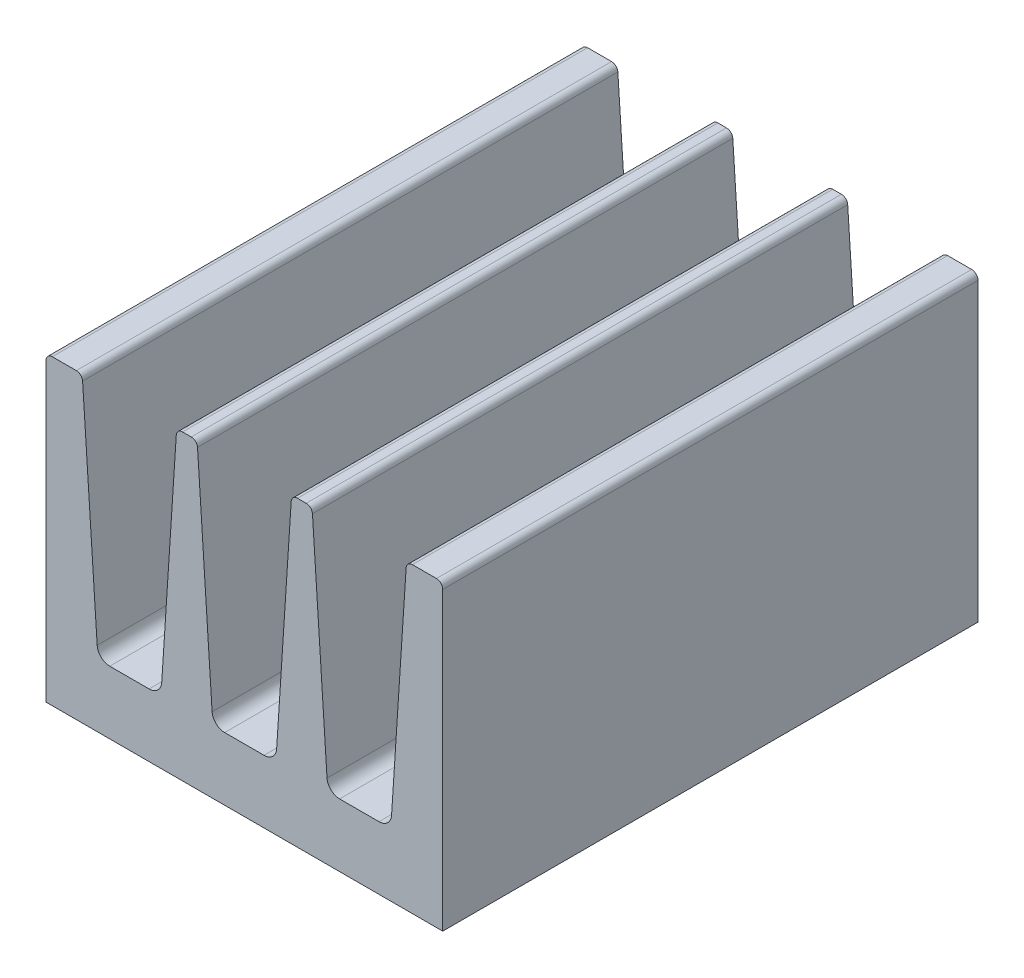
SolidWorks part; units mm, degrees
material "6061 Alloy"
ref_plane "Front Plane" through (0, 0, 0) normal (0, 0, 1) x (1, 0, 0)
ref_plane "Top Plane" through (0, 0, 0) normal (0, 1, 0) x (1, 0, 0)
ref_plane "Right Plane" through (0, 0, 0) normal (1, 0, 0) x (0, 0, -1)
sketch "Sketch1" plane through (0, 0, 0) normal (0, 1, 0) x (1, 0, 0)
  line L1 (0, 0) -> (6.3, 0)
  line L2 (0, 0) -> (0, 8.5)
  line L3 (0, 8.5) -> (6.3, 8.5)
  line L4 (6.3, 0) -> (6.3, 8.5)
  dimension "D1" = 6.3
  dimension "D2" = 8.5
extrude "Boss-Extrude1" add sketch "Sketch1" along normal blind 4.8
sketch "Sketch2" plane through (0, 4.8, 0) normal (0, 1, 0) x (1, 0, 0)
  line L0 (6.3, 8.5) -> (0, 8.5) construction
  line L1 (0.825, 8.5) -> (1.825, 8.5)
  line L2 (0.825, 8.5) -> (0.825, 0)
  line L3 (0.825, 0) -> (1.825, 0)
  line L4 (1.825, 8.5) -> (1.825, 0)
  line L5 (0, 0) -> (6.3, 0) construction
  line L6 (0, 8.5) -> (0, 0) construction
  line L7 (2.65, 8.5) -> (3.65, 8.5)
  line L8 (2.65, 8.5) -> (2.65, 0)
  line L9 (2.65, 0) -> (3.65, 0)
  line L10 (3.65, 8.5) -> (3.65, 0)
  line L11 (4.475, 8.5) -> (5.475, 8.5)
  line L12 (4.475, 8.5) -> (4.475, 0)
  line L13 (4.475, 0) -> (5.475, 0)
  line L14 (5.475, 8.5) -> (5.475, 0)
  dimension "D1" = 1
  dimension "D2" = 1
  dimension "D3" = 1
  dimension "D4" = 0.825
  dimension "D5" = 0.825
  dimension "D6" = 0.825
extrude "Cut-Extrude1" cut sketch "Sketch2" against normal blind 3.8
chamfer "Chamfer1" distance 0.25 distance2 3.8 6 edges at (0.825, 4.8, -4.25) (5.475, 4.8, -4.25) (4.475, 4.8, -4.25) (3.65, 4.8, -4.25) (2.65, 4.8, -4.25) (1.825, 4.8, -4.25) first distance on face at (0.4125, 4.8, -4.25) first distance on face at (5.8875, 4.8, -4.25) first distance on face at (4.0625, 4.8, -4.25) first distance on face at (2.2375, 4.8, -4.25)
fillet "Fillet1" radius 0.2 6 edges at (0.825, 1, -4.25) (1.825, 1, -4.25) (2.65, 1, -4.25) (3.65, 1, -4.25) (5.475, 1, -4.25) (4.475, 1, -4.25)
fillet "Fillet2" radius 0.1 8 edges at (0, 4.8, -4.25) (0.575, 4.8, -4.25) (2.075, 4.8, -4.25) (2.4, 4.8, -4.25) (3.9, 4.8, -4.25) (4.225, 4.8, -4.25) (5.725, 4.8, -4.25) (6.3, 4.8, -4.25)
